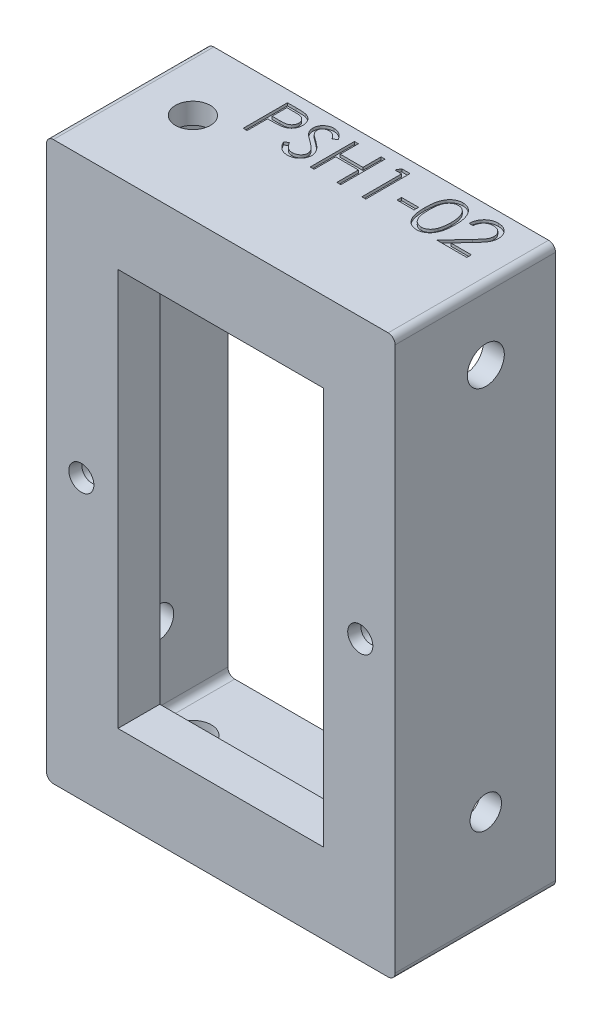
SolidWorks part; units mm, degrees
ref_plane "Front" through (0, 0, 0) normal (0, 0, 1) x (1, 0, 0)
ref_plane "Top" through (0, 0, 0) normal (0, 1, 0) x (1, 0, 0)
ref_plane "Right" through (0, 0, 0) normal (1, 0, 0) x (0, 0, -1)
sketch "Sketch3" plane through (0, 0, 0) normal (0, 0, 1) x (1, 0, 0)
  line L0 (10.9, 16.4) -> (0, 16.4) construction
  line L1 (0, 0) -> (50, 0)
  line L2 (0, 0) -> (0, 80)
  line L3 (0, 80) -> (50, 80)
  line L4 (50, 0) -> (50, 80)
  line L5 (10.9, 16.4) -> (39.1, 16.4)
  line L6 (10.9, 16.4) -> (10.9, 63.6)
  line L7 (10.9, 63.6) -> (39.1, 63.6)
  line L8 (39.1, 16.4) -> (39.1, 63.6)
  line L9 (39.1, 16.4) -> (50, 16.4) construction
  line L10 (10.9, 16.4) -> (10.9, 0) construction
  line L11 (10.9, 63.6) -> (10.9, 80) construction
  line L12 (25, 63.6) -> (25, 40) construction
  line L13 (25, 40) -> (25, 16.4) construction
  line L14 (25, 40) -> (5, 40) construction
  line L15 (25, 40) -> (45, 40) construction
  circle A0 centre (5, 40) radius 1.4 construction
  circle A1 centre (45, 40) radius 1.4 construction
  dimension "D5" = 40
  dimension "D6" = 2.8
  dimension "D1" = 50
  dimension "D2" = 80
  dimension "D3" = 28.2
  dimension "D4" = 47.2
extrude "Boss-Extrude1" add sketch "Sketch3" along normal blind 23
sketch "Sketch4" plane through (0, 0, 0) normal (0, 0, -1) x (-1, 0, 0)
  line L8 (-47, 3) -> (-3, 3)
  line L9 (-3, 3) -> (-3, 77)
  line L10 (-47, 77) -> (-47, 3)
  line L11 (-3, 77) -> (-47, 77)
  line L12 (-47, 3) -> (-3, 3)
  line L13 (-3, 3) -> (-3, 77)
  line L14 (-47, 77) -> (-47, 3)
  line L15 (-3, 77) -> (-47, 77)
  dimension "D1" = 3
extrude "Cut-Extrude1" cut sketch "Sketch4" against normal offset from surface (17 mm away) 6 up to face at (25, 40, 23)
sketch "Sketch17" plane through (0, 0, 23) normal (0, 0, 1) x (1, 0, 0)
  circle A0 centre (45, 40) radius 1.4 construction
  circle A1 centre (5, 40) radius 1.4 construction
  circle A2 centre (45, 40) radius 1.4
  circle A3 centre (5, 40) radius 1.4
extrude "Cut-Extrude7" cut sketch "Sketch17" against normal through all
chamfer "Chamfer1" distance 0.4 angle 75 2 edges at (46.4, 40, 23) (6.4, 40, 23) first distance on face at (46.4, 40, 23)
fillet "Fillet1" radius 1 4 edges at (0, 0, 11.5) (50, 0, 11.5) (50, 80, 11.5) (0, 80, 11.5)
fillet "Fillet2" radius 1 4 edges at (47, 3, 8.5) (3, 3, 8.5) (3, 77, 8.5) (47, 77, 8.5)
sketch "Sketch5" plane through (0, 0, 0) normal (-1, 0, 0) x (0, 0, 1)
  line L0 (0, 79) -> (0, 1) construction
  line L1 (0, 80) -> (23, 80) construction
  line L2 (10, 70) -> (10, 45) construction
  line L3 (10, 45) -> (10, 14.5) construction
  circle A0 centre (10, 70) radius 2.5
  circle A2 centre (10, 14.5) radius 2.25
  dimension "D1" = 10
  dimension "D2" = 5
  dimension "D3" = 10
  dimension "D4" = 25
  dimension "D5" = 14.5
  dimension "D6" = 4.5
extrude "Cut-Extrude2" cut sketch "Sketch5" against normal up to next
hole_wizard "M5 Clearance Hole1" positions "Sketch6" profile "Sketch7" hole size "M5" standard "ANSI Metric" end condition up to next
sketch "Sketch6" plane through (47, 0, 0) normal (-1, 0, 0) x (0, 0, 1)
  point P0 (10, 70)
sketch "Sketch7" plane through (47, 70, 10) normal (0, 1, 0) x (0, 0, 1)
  line L0 (0, 0) -> (0, 3)
  line L1 (0, 3) -> (2.65, 3)
  line L2 (2.65, 3) -> (2.65, 0)
  line L5 (2.65, 0) -> (0, 0)
  line L11 (0, -6.35) -> (0, 107.95) construction
  dimension "Thru Hole Dia." = 5.3
  dimension "Thru Hole Depth" = 3
sketch "Sketch8" plane through (0, 80, 0) normal (0, 1, 0) x (1, 0, 0)
  line L0 (49, 0) -> (1, 0) construction
  line L1 (0, -23) -> (0, 0) construction
  circle A0 centre (8, -10) radius 2.5
  dimension "D1" = 5
  dimension "D3" = 8
  dimension "D2" = 10
extrude "Cut-Extrude3" cut sketch "Sketch8" against normal up to next
hole_wizard "M5 Clearance Hole2" positions "Sketch10" profile "Sketch11" hole size "M5" standard "ANSI Metric" end condition up to next
sketch "Sketch10" plane through (0, 3, 0) normal (0, 1, 0) x (1, 0, 0)
  point P0 (8, -10)
sketch "Sketch11" plane through (8, 3, 10) normal (1, 0, 0) x (0, 0, 1)
  line L0 (0, 0) -> (0, 3)
  line L1 (0, 3) -> (2.65, 3)
  line L2 (2.65, 3) -> (2.65, 0)
  line L5 (2.65, 0) -> (0, 0)
  line L11 (0, -6.35) -> (0, 107.95) construction
  dimension "Thru Hole Dia." = 5.3
  dimension "Thru Hole Depth" = 3
sketch "Sketch12" plane through (47, 0, 0) normal (-1, 0, 0) x (0, 0, 1)
  circle A0 centre (10, 14.5) radius 2.25 construction
  circle A1 centre (10, 14.5) radius 2.25
extrude "Cut-Extrude4" cut sketch "Sketch12" against normal through all
sketch "Sketch13" plane through (0, 80, 0) normal (0, 1, 0) x (1, 0, 0)
  line L0 (8, -8) -> (50, -8) construction
  line L1 (50, 0) -> (50, -23) construction
  line L2 (49, 0) -> (1, 0) construction
  text T0 "PSH1-02"
  dimension "D1" = 8
extrude "Part Number" cut sketch "Sketch13" against normal blind 0.4
sketch "Sketch14" plane through (0, 0, 23) normal (0, 0, 1) x (1, 0, 0)
  line L1 (10.25, 68.5) -> (39.75, 68.5)
  line L2 (10.25, 68.5) -> (10.25, 11.5)
  line L3 (10.25, 11.5) -> (39.75, 11.5)
  line L4 (39.75, 68.5) -> (39.75, 11.5)
  line L6 (25, 68.5) -> (25, 63.6) construction
  line L7 (39.1, 63.6) -> (10.9, 63.6) construction
  line L8 (25, 11.5) -> (25, 16.4) construction
  line L9 (10.9, 16.4) -> (39.1, 16.4) construction
  dimension "D1" = 57
  dimension "D2" = 29.5
extrude "Omnicom Enlarged Socket Cavity" cut sketch "Sketch14" against normal through all
sketch "Sketch15" [suppressed] plane through (0, 0, 23) normal (0, 0, 1) x (1, 0, 0)
  line L0 (25, 40) -> (39.1, 40) construction
  line L1 (10, 9.5) -> (40, 9.5)
  line L2 (10, 9.5) -> (10, 70.5)
  line L3 (10, 70.5) -> (40, 70.5)
  line L4 (40, 9.5) -> (40, 70.5)
  line L5 (10, 9.5) -> (40, 70.5) construction
  line L6 (10, 70.5) -> (40, 9.5) construction
  line L7 (39.1, 16.4) -> (39.1, 63.6) construction
  line L8 (25, 40) -> (10.9, 40) construction
  line L9 (10.9, 63.6) -> (10.9, 16.4) construction
  point P0 (25, 40)
  dimension "D1" = 61
  dimension "D2" = 30
extrude "Astrodyne Enlarged Socket Cavity" [suppressed] cut sketch "Sketch15" against normal through all
sketch "Sketch16" [suppressed] plane through (0, 0, 23) normal (0, 0, 1) x (1, 0, 0)
  line L0 (25, 76) -> (25, 70.5) construction
  line L1 (40, 70.5) -> (10, 70.5) construction
  line L2 (25, 4) -> (25, 9.5) construction
  line L3 (10, 9.5) -> (40, 9.5) construction
  circle A0 centre (25, 76) radius 1.4
  circle A1 centre (25, 4) radius 1.4
  dimension "D1" = 72
  dimension "D2" = 2.8
extrude "Cut-Extrude6" [suppressed] cut sketch "Sketch16" against normal through all
chamfer "Chamfer2" [suppressed] distance 0.4 angle 70
ref_plane "Plane1" [suppressed] through (0, 0, 10) normal (0, 0, 1) x (1, 0, 0)
sketch "Sketch18" [suppressed] plane through (0, 0, 10) normal (0, 0, 1) x (1, 0, 0)
  line L0 (47, 70) -> (46.2, 70) construction
  line L1 (47, 72.65) -> (47, 67.35) construction
  line L2 (46.2, 70) -> (-6.9259, 84.235) construction
  line L3 (46.2, 70) -> (26.1844, 70) construction
  dimension "D1" = 15
  dimension "D2" = 55
  dimension "D3" = 0.8
ref_plane "Plane2" [suppressed] through (-6.9259, 84.235, 10) normal (-0.9659, 0.2588, 0) x (0, 0, 1)
sketch "Sketch19" [suppressed] plane through (-6.9259, 84.235, 10) normal (-0.9659, 0.2588, 0) x (0, 0, 1)
  line L0 (0, 0) -> (0, -5.1804) construction
  circle A0 centre (0, 0) radius 2
  dimension "D1" = 4
extrude "Cut-Extrude8" [suppressed] cut sketch "Sketch19" against normal up to surface (56.3641 mm away) up to face at (47, 14.5, 12.25)
